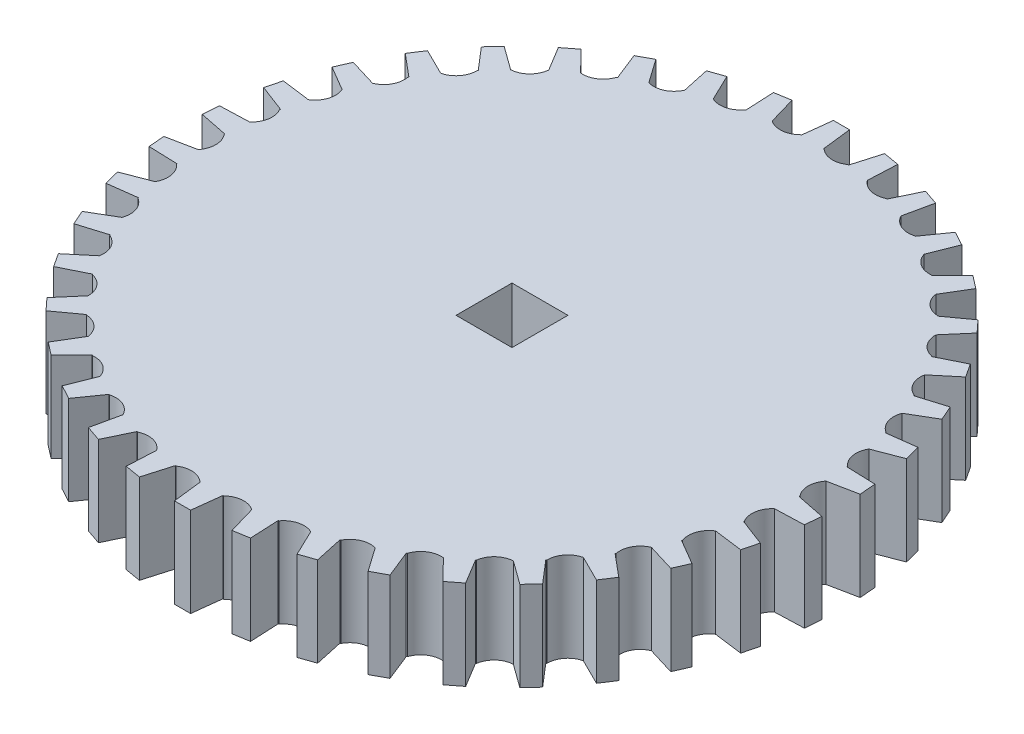
SolidWorks part; units mm, degrees
ref_plane "Front Plane" through (0, 0, 0) normal (0, 0, 1) x (1, 0, 0)
ref_plane "Top Plane" through (0, 0, 0) normal (0, 1, 0) x (1, 0, 0)
ref_plane "Right Plane" through (0, 0, 0) normal (1, 0, 0) x (0, 0, -1)
sketch "Sketch1" plane through (0, 0, 0) normal (0, 1, 0) x (1, 0, 0)
  circle A0 centre (0, 0) radius 21.336
  dimension "D1" = 42.672
extrude "Boss-Extrude1" add sketch "Sketch1" along normal blind 6.35
ref_axis "Axis1" through (0, 6.35, 0) along (0, -1, 0)
sketch "Sketch2" plane through (0, 6.35, 0) normal (0, 1, 0) x (1, 0, 0)
  line L0 (-0.5715, 23.368) -> (0.5715, 23.368)
  line L1 (0.5715, 23.368) -> (0.8129, 21.3205)
  line L2 (-0.5715, 23.368) -> (-0.8129, 21.3205)
  circle A0 centre (0, 0) radius 21.336 construction
  arc A1 (0.8129, 21.3205) -> (2.6544, 21.1702) centre (1.8249, 22.3628) ccw
  arc A4 (0.8129, 21.3205) -> (2.6544, 21.1702) centre (0, 0) cw
  arc A5 (-0.8129, 21.3205) -> (2.6544, 21.1702) centre (0, 0) cw
  point P2 (0, 23.368)
  circle M6 centre (0, 0) radius 21.336
  dimension "D5" = 1.4527
  dimension "D1" = 1.143
  dimension "D2" = 23.368
  dimension "D4" = 1.8415
extrude "Boss-Extrude2" add sketch "Sketch2" against normal up to surface (6.35 mm away) contours L0 L2 L1 M6 region at (0, 6.35, -22.2905) up to face at (0, 0, 21.336)
extrude "Cut-Extrude1" cut sketch "Sketch2<4>" against normal through all contours A4 A1 region at (1.7234, 6.35, -21.1197)
sketch "Sketch2<4>" plane through (0, 6.35, 0) normal (0, 1, 0) x (1, 0, 0) same geometry as "Sketch2"
pattern_circular "CirPattern1" count 38 over 360 about axis through (0, 6.35, 0) along (0, -1, 0) of "Boss-Extrude2", "Cut-Extrude1"
sketch "Sketch3" plane through (0, 6.35, 0) normal (0, 1, 0) x (1, 0, 0)
  line L1 (-1.9838, -1.9838) -> (1.9838, -1.9838)
  line L2 (-1.9838, -1.9838) -> (-1.9838, 1.9838)
  line L3 (-1.9838, 1.9838) -> (1.9838, 1.9838)
  line L4 (1.9838, -1.9838) -> (1.9838, 1.9838)
  line L5 (-1.9838, -1.9838) -> (1.9838, 1.9838) construction
  line L6 (-1.9838, 1.9838) -> (1.9838, -1.9838) construction
  point P0 (0, 0)
  dimension "D1" = 3.9676
extrude "Cut-Extrude2" cut sketch "Sketch3" against normal through all
